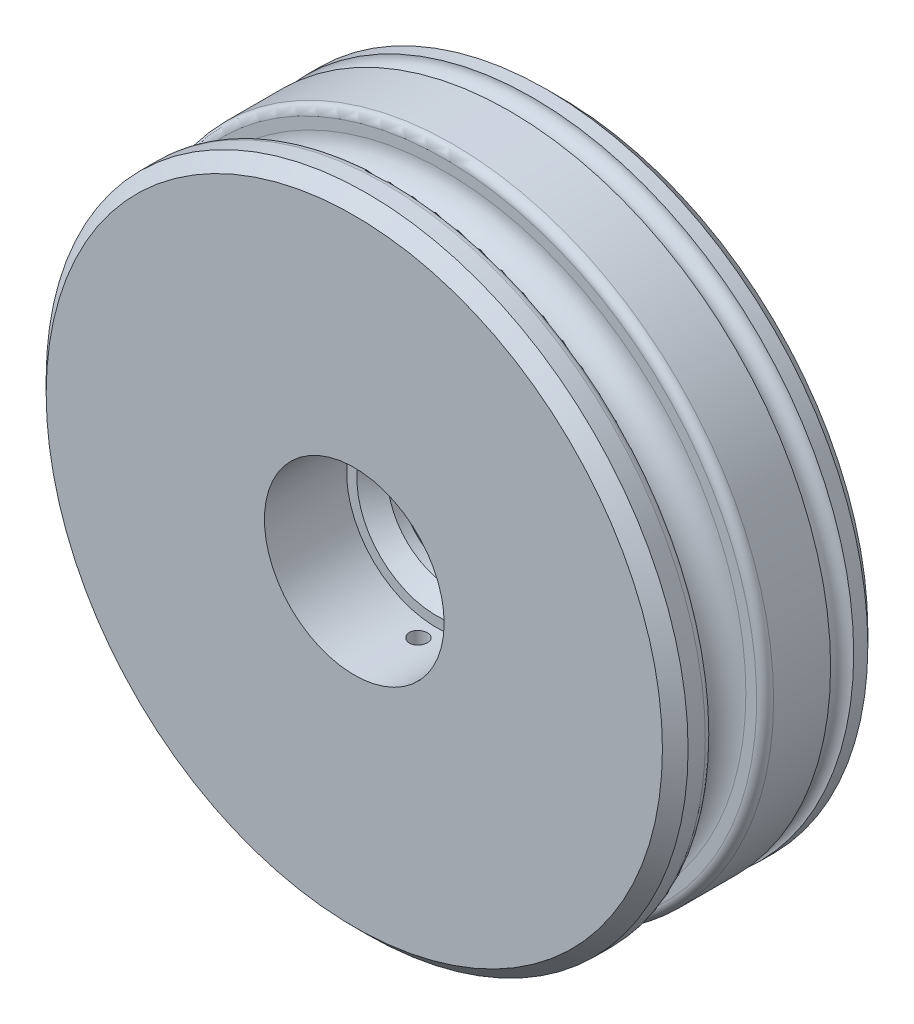
SolidWorks part; units mm, degrees
ref_plane "Front Plane" through (0, 0, 0) normal (0, 0, 1) x (1, 0, 0)
ref_plane "Top Plane" through (0, 0, 0) normal (0, 1, 0) x (1, 0, 0)
ref_plane "Right Plane" through (0, 0, 0) normal (1, 0, 0) x (0, 0, -1)
sketch "Sketch1" plane through (0, 0, 0) normal (0, 0, 1) x (1, 0, 0)
  circle A0 centre (0, 0) radius 12.5
  dimension "D1" = 25
extrude "Boss-Extrude1" add sketch "Sketch1" along normal blind 4
sketch "Sketch3" plane through (0, 0, 0) normal (1, 0, 0) x (0, 0, -1)
  line L1 (-4, 12.5) -> (-4, -12.5) construction
  line L3 (0, 12.5) -> (-4, 12.5) construction
  line L4 (-2.5, 11.75) -> (-2.5, 12.75)
  line L5 (-2.5, 12.75) -> (-0.5, 12.75)
  line L6 (-0.5, 12.75) -> (-0.5, 11.75)
  arc A0 (-2.5, 11.75) -> (-0.5, 11.75) centre (-1.5, 11.75) ccw
  point P5 (0, 0)
  point P6 (0, 0)
  dimension "D1" = 2
  dimension "D2" = 2.5
  dimension "D3" = 0.75
ref_axis "Axis1" through (0, 0, -0.35) along (0, 0, 1)
revolve "Cut-Revolve1" cut sketch "Sketch3" angle 360 about axis through (0, 0, -0.35) along (0, 0, 1)
sketch "Sketch2" plane through (0, 0, 4) normal (0, 0, 1) x (1, 0, 0)
  circle A0 centre (0, 0) radius 3.5
  dimension "D1" = 7
extrude "Cut-Extrude1" cut sketch "Sketch2" against normal blind 3.2
chamfer "Chamfer1" distance 0.5 angle 45 1 edges at (12.5, 0, 4)
sketch "Sketch4" plane through (0, 0, 0.8) normal (0, 0, 1) x (1, 0, 0)
  circle A0 centre (0, 0) radius 2.5
  dimension "D1" = 5
extrude "Cut-Extrude2" cut sketch "Sketch4" against normal through all
ref_axis "Axis2" through (0, 55, 4) along (0, -1, 0)
sketch "Sketch6" plane through (0, 0, 0) normal (1, 0, 0) x (0, 0, -1)
  line L0 (-4, 55) -> (-4, -55) construction
  line L1 (-4, 9) -> (-4, 11)
  line L2 (-2.5, 12.5) -> (-3.5, 12.5) construction
  arc A0 (-4, 11) -> (-4, 9) centre (-4, 10) ccw
  dimension "D1" = 2
  dimension "D2" = 2.5
revolve "Revolve1" [suppressed] add sketch "Sketch6" angle 360 about axis through (0, 55, 4) along (0, -1, 0)
chamfer "Chamfer2" distance 0.6 angle 45 1 edges at (2.5, 0, 0.8)
pattern_circular "CirPattern1" [suppressed] count 15 over 360 about axis through (0, 0, -0.35) along (0, 0, 1) reverse direction yes of bodies 110
mirror "Mirror2" about plane through (0, 0, 0) normal (0, 0, 1) of "Cut-Extrude2", "Chamfer1", "Cut-Extrude1", "Boss-Extrude1", "Chamfer2"
sketch "Sketch7" plane through (0, 0, 0) normal (1, 0, 0) x (0, 0, -1)
  line L0 (3.5, 12.5) -> (-0.5, 12.5) construction
  line L1 (3.5, -12.5) -> (3.5, 12.5) construction
  circle A0 centre (2.5, 12.5) radius 0.45
  dimension "D1" = 0.9
  dimension "D2" = 1
revolve "Cut-Revolve3" cut sketch "Sketch7" angle 360 about axis through (0, 0, -0.35) along (0, 0, 1)
fillet "Fillet1" radius 0.33 2 edges at (12.5, 0, 2.5) (-12.5, 0, 0.5)
sketch "Sketch8" plane through (0, 0, 0) normal (0, 1, 0) x (1, 0, 0)
  circle A0 centre (0, -1.5) radius 0.35
  point P2 (0, 0)
  dimension "D1" = 0.7
extrude "Cut-Extrude3" cut sketch "Sketch8" against normal through all
ref_plane "Plane1" through (0, 0, 1.5) normal (0, 0, 1) x (1, 0, 0)
